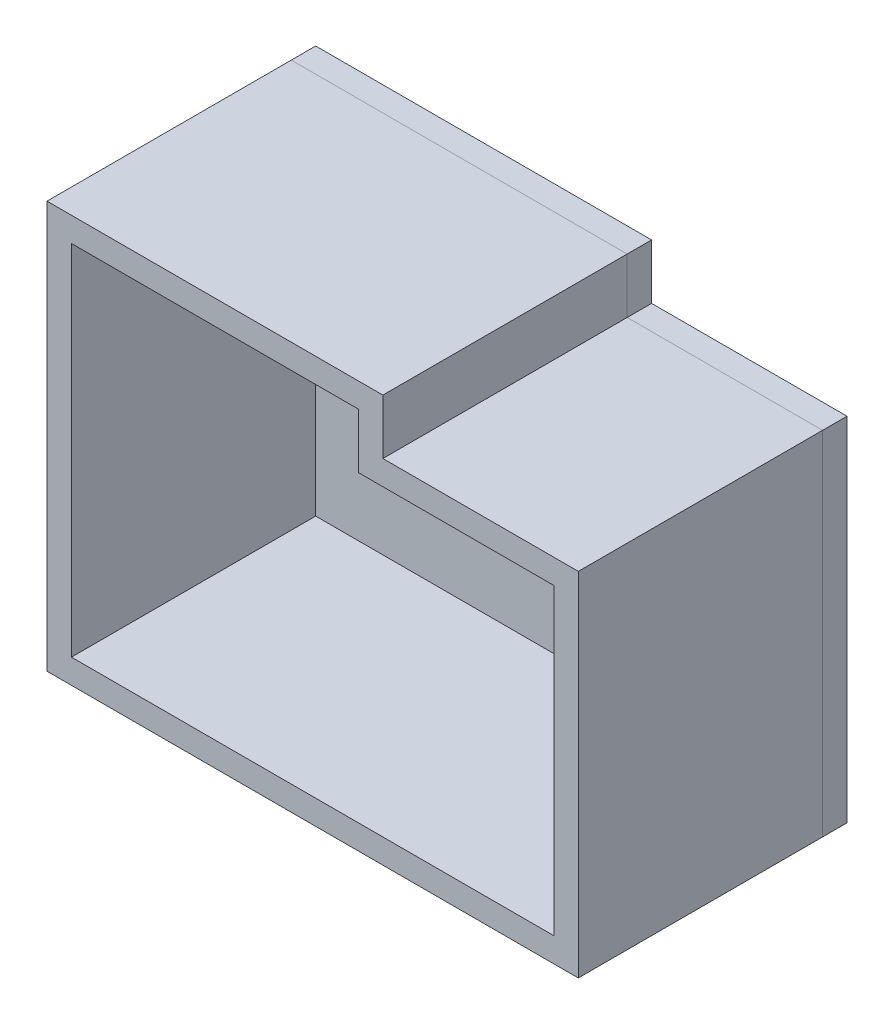
SolidWorks part; units mm, degrees
material "Ceramic Porcelain"
ref_plane "Front Plane" through (0, 0, 0) normal (0, 0, 1) x (1, 0, 0)
ref_plane "Top Plane" through (0, 0, 0) normal (0, 1, 0) x (1, 0, 0)
ref_plane "Right Plane" through (0, 0, 0) normal (1, 0, 0) x (0, 0, -1)
sketch "Sketch1" plane through (0, 0, 0) normal (0, 0, 1) x (1, 0, 0)
  line L0 (3581.4, 4470.4) -> (3581.4, 3784.6)
  line L1 (0, 0) -> (6019.8, 0)
  line L2 (0, 0) -> (0, 4470.4)
  line L3 (0, 4470.4) -> (6019.8, 4470.4) construction
  line L4 (6019.8, 0) -> (6019.8, 4470.4) construction
  line L5 (3581.4, 3784.6) -> (6019.8, 3784.6)
  line L6 (0, 4470.4) -> (3581.4, 4470.4)
  line L7 (6019.8, 3784.6) -> (6019.8, 0)
  dimension "D1" = 6019.8
  dimension "D2" = 4470.4
  dimension "D3" = 685.8
  dimension "D4" = 2438.4
extrude "Extrude-Thin2" add sketch "Sketch1" along normal blind 3048 thin thin type one direction wall 304.8
sketch "Sketch3" plane through (0, 0, 0) normal (0, 0, -1) x (-1, 0, 0)
  line L0 (304.8, 4775.2) -> (-3886.2, 4775.2)
  line L1 (-3886.2, 4775.2) -> (-3886.2, 4089.4)
  line L2 (-3886.2, 4089.4) -> (-6324.6, 4089.4)
  line L3 (-6324.6, 4089.4) -> (-6324.6, -304.8)
  line L4 (-6324.6, -304.8) -> (304.8, -304.8)
  line L5 (304.8, -304.8) -> (304.8, 4775.2)
  line M1 (304.8, -304.8) -> (304.8, 4775.2)
  line M2 (304.8, 4775.2) -> (-3886.2, 4775.2)
  line M3 (-3886.2, 4775.2) -> (-3886.2, 4089.4)
  line M4 (-3886.2, 4089.4) -> (-6324.6, 4089.4)
  line M5 (-6324.6, 4089.4) -> (-6324.6, -304.8)
  line M6 (-6324.6, -304.8) -> (304.8, -304.8)
  line M7 (0, 4470.4) -> (0, 0)
  line M8 (0, 0) -> (-6019.8, 0)
  line M9 (-6019.8, 0) -> (-6019.8, 3784.6)
  line M10 (-6019.8, 3784.6) -> (-3581.4, 3784.6)
  line M11 (-3581.4, 3784.6) -> (-3581.4, 4470.4)
  line M12 (-3581.4, 4470.4) -> (0, 4470.4)
extrude "Boss-Extrude1" add sketch "Sketch3" along normal blind 304.8 separate body contours M7 M12 M11 M10 M9 M8 | M6 M1 M2 M3 M4 M5 M12 M7 M8 M9 M10 M11 region at (-221.2803, 2235.2, 0) region at (2891.2524, 2109.8206, 0)
